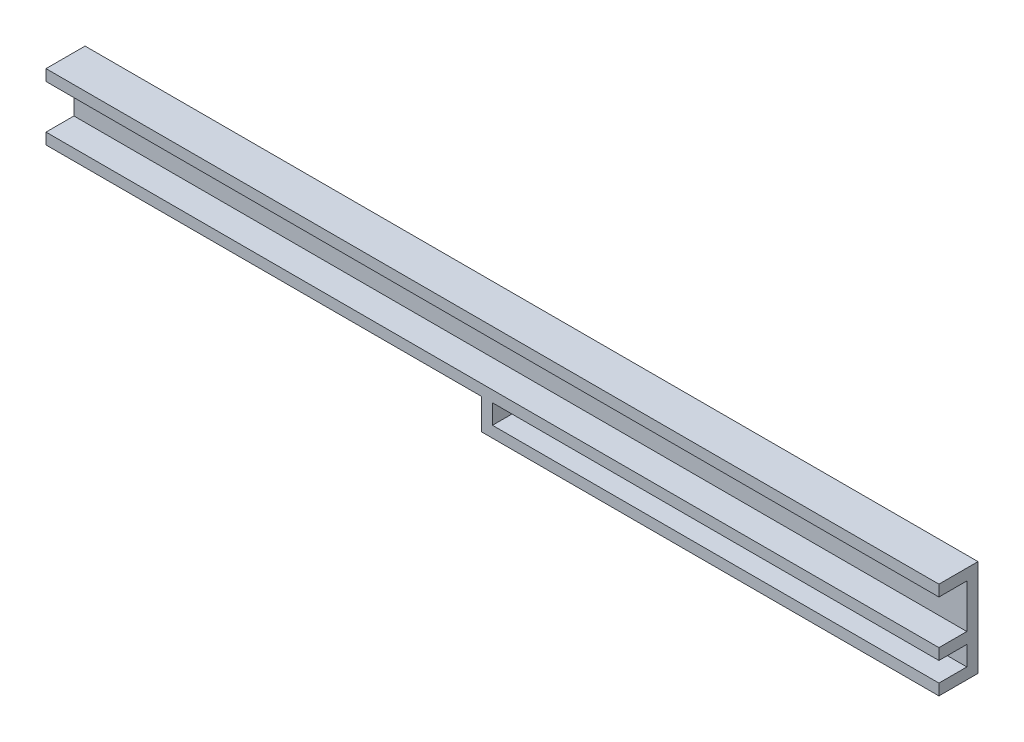
SolidWorks part; units mm, degrees
ref_plane "Plano frontal" through (0, 0, 0) normal (0, 0, 1) x (1, 0, 0)
ref_plane "Plano superior" through (0, 0, 0) normal (0, 1, 0) x (1, 0, 0)
ref_plane "Plano direito" through (0, 0, 0) normal (1, 0, 0) x (0, 0, -1)
sketch "Esboço1" plane through (0, 0, 0) normal (0, 0, 1) x (1, 0, 0)
  line L1 (-39.2322, 14.3911) -> (120.7678, 14.3911)
  line L2 (-39.2322, 14.3911) -> (-39.2322, 6.5411)
  line L3 (-39.2322, 6.5411) -> (120.7678, 6.5411)
  line L4 (120.7678, 14.3911) -> (120.7678, 6.5411)
  line L5 (-39.2322, 14.3911) -> (120.7678, 14.3911)
  line L6 (-39.2322, 14.3911) -> (-39.2322, 16.3911)
  line L7 (-39.2322, 16.3911) -> (120.7678, 16.3911)
  line L8 (120.7678, 14.3911) -> (120.7678, 16.3911)
  line L9 (120.7678, 6.5411) -> (-39.2322, 6.5411)
  line L10 (120.7678, 6.5411) -> (120.7678, 4.5411)
  line L11 (120.7678, 4.5411) -> (-39.2322, 4.5411)
  line L12 (-39.2322, 6.5411) -> (-39.2322, 4.5411)
  line L13 (40.7678, 4.5411) -> (120.7678, 4.5411)
  line L14 (40.7678, 4.5411) -> (40.7678, 1.0411)
  line L15 (40.7678, 1.0411) -> (120.7678, 1.0411)
  line L16 (120.7678, 4.5411) -> (120.7678, 1.0411)
  line L17 (120.7678, 1.0411) -> (40.7678, 1.0411)
  line L18 (120.7678, 1.0411) -> (120.7678, -0.9589)
  line L19 (120.7678, -0.9589) -> (40.7678, -0.9589)
  line L20 (40.7678, 1.0411) -> (40.7678, -0.9589)
  line L21 (40.7678, 4.5411) -> (38.7678, 4.5411)
  line L22 (40.7678, 4.5411) -> (40.7678, -0.9589)
  line L23 (40.7678, -0.9589) -> (38.7678, -0.9589)
  line L24 (38.7678, 4.5411) -> (38.7678, -0.9589)
  dimension "D1" = 160
  dimension "D2" = 2
  dimension "D3" = 2
  dimension "D4" = 2
  dimension "D5" = 7.85
  dimension "D6" = 3.5
  dimension "D7" = 2
extrude "Ressalto-extrusão1" add sketch "Esboço1" along normal blind 5 contours L1 L8 L7 L6 | L3 L12 L11 L10 | L15 L20 L19 L18 | L11 L24 L23 L20 L14 region at (40.7678, 15.3911, 0) region at (40.7678, 5.5411, 0) region at (39.7678, 1.7911, 0) region at (80.7678, 0.0411, 0)
extrude "Ressalto-extrusão2" add sketch "Esboço1<3>" against normal blind 2 contours L4 L1 L2 L3 | L16 L11 L14 L15 | L1 L8 L7 L6 | L3 L12 L11 L10 | L15 L20 L19 L18 | L11 L24 L23 L20 L14 region at (40.7678, 15.3911, 0) region at (40.7678, 10.4661, 0) region at (40.7678, 5.5411, 0) region at (80.7678, 2.7911, 0) region at (39.7678, 1.7911, 0) region at (80.7678, 0.0411, 0)
sketch "Esboço1<3>" plane through (0, 0, 0) normal (0, 0, 1) x (1, 0, 0) same geometry as "Esboço1"
